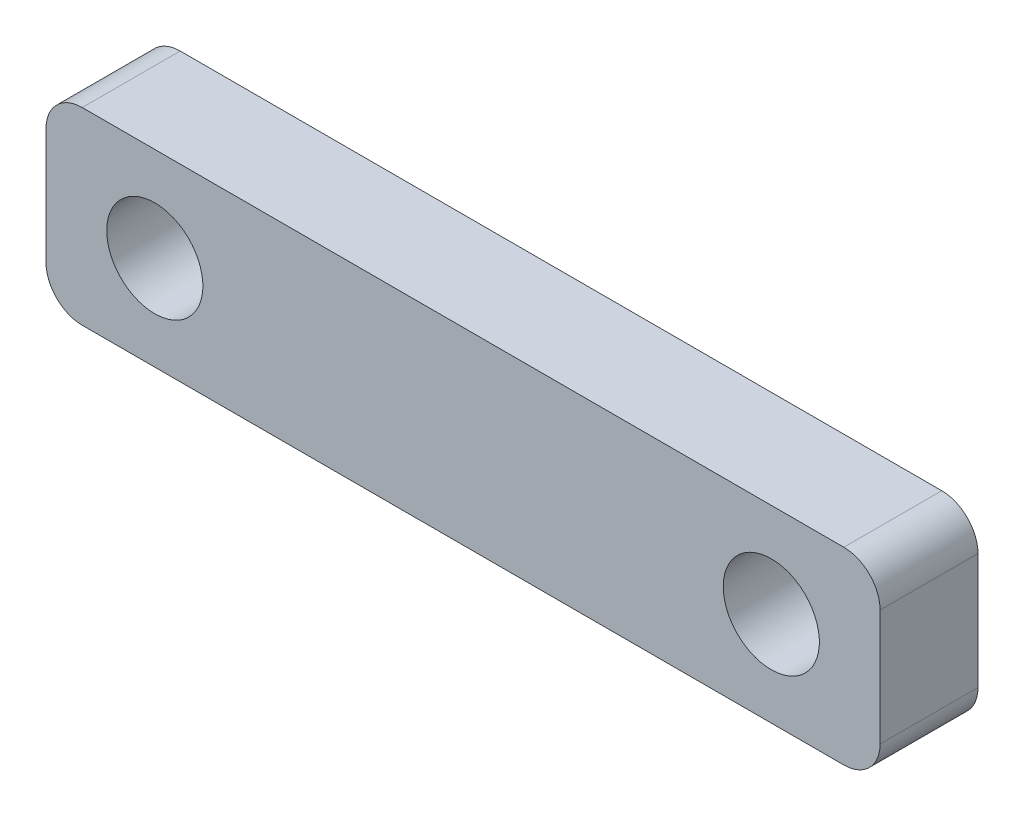
SolidWorks part; units mm, degrees
ref_plane "Front Plane" through (0, 0, 0) normal (0, 0, 1) x (1, 0, 0)
ref_plane "Top Plane" through (0, 0, 0) normal (0, 1, 0) x (1, 0, 0)
ref_plane "Right Plane" through (0, 0, 0) normal (1, 0, 0) x (0, 0, -1)
sketch "Sketch2" plane through (0, 0, 0) normal (0, 0, 1) x (1, 0, 0)
  line L0 (-8.5, 0) -> (8.5, 0) construction
  line L1 (-11.5, 2.6) -> (11.5, 2.6)
  line L2 (-11.5, 2.6) -> (-11.5, -2.6)
  line L3 (-11.5, -2.6) -> (11.5, -2.6)
  line L4 (11.5, 2.6) -> (11.5, -2.6)
  line L5 (-11.5, 2.6) -> (11.5, -2.6) construction
  line L6 (-11.5, -2.6) -> (11.5, 2.6) construction
  circle A0 centre (-8.5, 0) radius 1.325
  circle A1 centre (8.5, 0) radius 1.325
  point P0 (0, 0)
  point P8 (0, 0)
  dimension "D6" = 2.65
  dimension "D1" = 23
  dimension "D2" = 5.2
  dimension "D3" = 2.6
  dimension "D4" = 17
extrude "Boss-Extrude1" add sketch "Sketch2" along normal blind 2.7
fillet "Fillet1" radius 1 4 edges at (-11.5, 2.6, 1.35) (-11.5, -2.6, 1.35) (11.5, -2.6, 1.35) (11.5, 2.6, 1.35)
